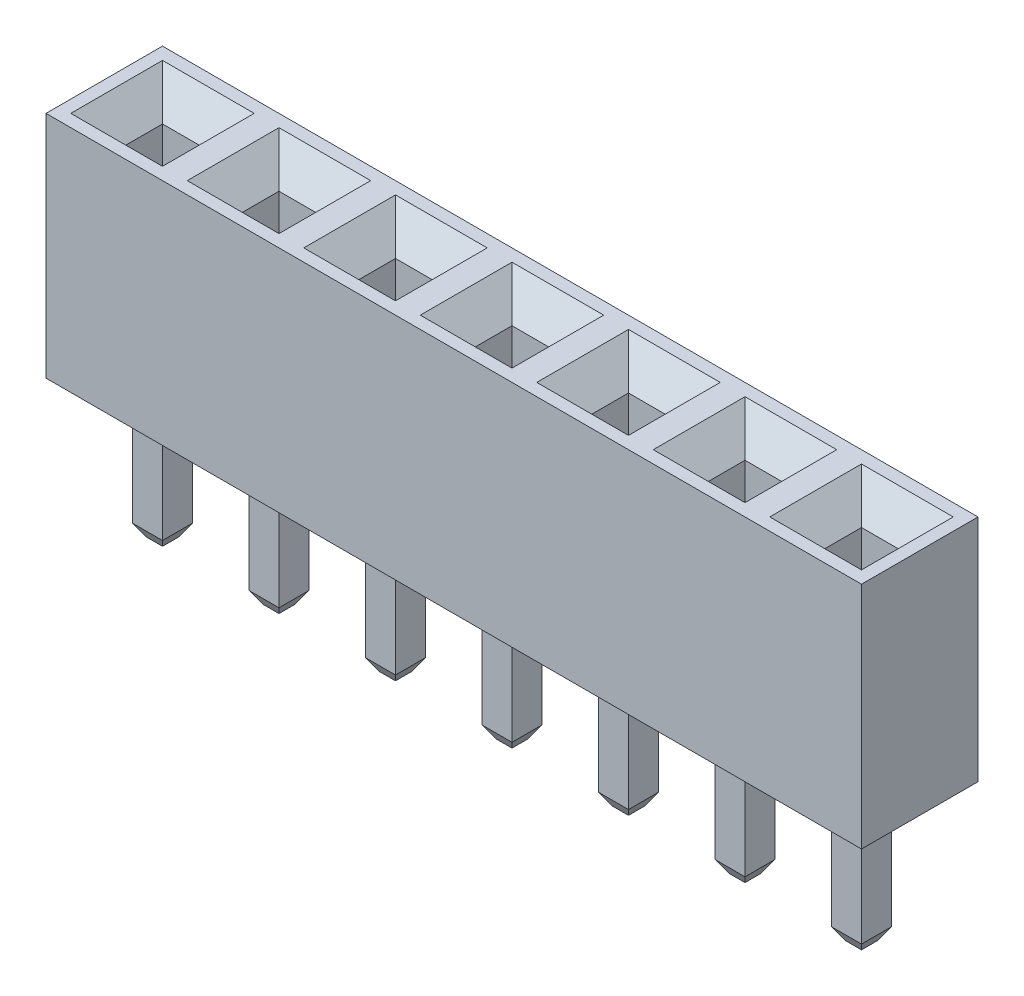
SolidWorks part; units mm, degrees
ref_plane "Front Plane" through (0, 0, 0) normal (0, 0, 1) x (1, 0, 0)
ref_plane "Top Plane" through (0, 0, 0) normal (0, 1, 0) x (1, 0, 0)
ref_plane "Right Plane" through (0, 0, 0) normal (1, 0, 0) x (0, 0, -1)
sketch "Sketch1" plane through (0, 0, 0) normal (0, 1, 0) x (1, 0, 0)
  line L1 (-1.27, 1.27) -> (1.27, 1.27)
  line L2 (-1.27, 1.27) -> (-1.27, -1.27)
  line L3 (-1.27, -1.27) -> (1.27, -1.27)
  line L4 (1.27, 1.27) -> (1.27, -1.27)
  line L5 (-1.27, 1.27) -> (1.27, -1.27) construction
  line L6 (-1.27, -1.27) -> (1.27, 1.27) construction
  point P0 (0, 0)
  dimension "D1" = 2.54
extrude "Boss-Extrude1" add sketch "Sketch1" along normal blind 5
sketch "Sketch2" plane through (0, 0, 0) normal (0, -1, 0) x (1, 0, 0)
  line L1 (-0.325, 0.325) -> (0.325, 0.325)
  line L2 (-0.325, 0.325) -> (-0.325, -0.325)
  line L3 (-0.325, -0.325) -> (0.325, -0.325)
  line L4 (0.325, 0.325) -> (0.325, -0.325)
  line L5 (-0.325, 0.325) -> (0.325, -0.325) construction
  line L6 (-0.325, -0.325) -> (0.325, 0.325) construction
  point P0 (0, 0)
  dimension "D1" = 0.65
extrude "Boss-Extrude2" add sketch "Sketch2" along normal blind 3
chamfer "Chamfer1" distance 0.15 angle 60 4 edges at (0, -3, -0.325) (-0.325, -3, 0) (0, -3, 0.325) (0.325, -3, 0) first distance on face at (0, -3, 0)
sketch "Sketch3" plane through (0, 5, 0) normal (0, 1, 0) x (1, 0, 0)
  line L1 (-0.4, 0.4) -> (0.4, 0.4)
  line L2 (-0.4, 0.4) -> (-0.4, -0.4)
  line L3 (-0.4, -0.4) -> (0.4, -0.4)
  line L4 (0.4, 0.4) -> (0.4, -0.4)
  line L5 (-0.4, 0.4) -> (0.4, -0.4) construction
  line L6 (-0.4, -0.4) -> (0.4, 0.4) construction
  point P0 (0, 0)
  dimension "D1" = 0.8
extrude "Cut-Extrude1" cut sketch "Sketch3" against normal blind 3
chamfer "Chamfer2" distance 0.6 angle 45 4 edges at (-0.4, 5, 0) (0, 5, 0.4) (0.4, 5, 0) (0, 5, -0.4)
pattern_linear "LPattern1" count 7 spacing 2.54 along (1, 0, 0) of "Boss-Extrude1", "Boss-Extrude2", "Cut-Extrude1", "Chamfer2", "Chamfer1"
ref_axis "Axis1" through (0, -5.675, 0) along (0, 1, 0)
